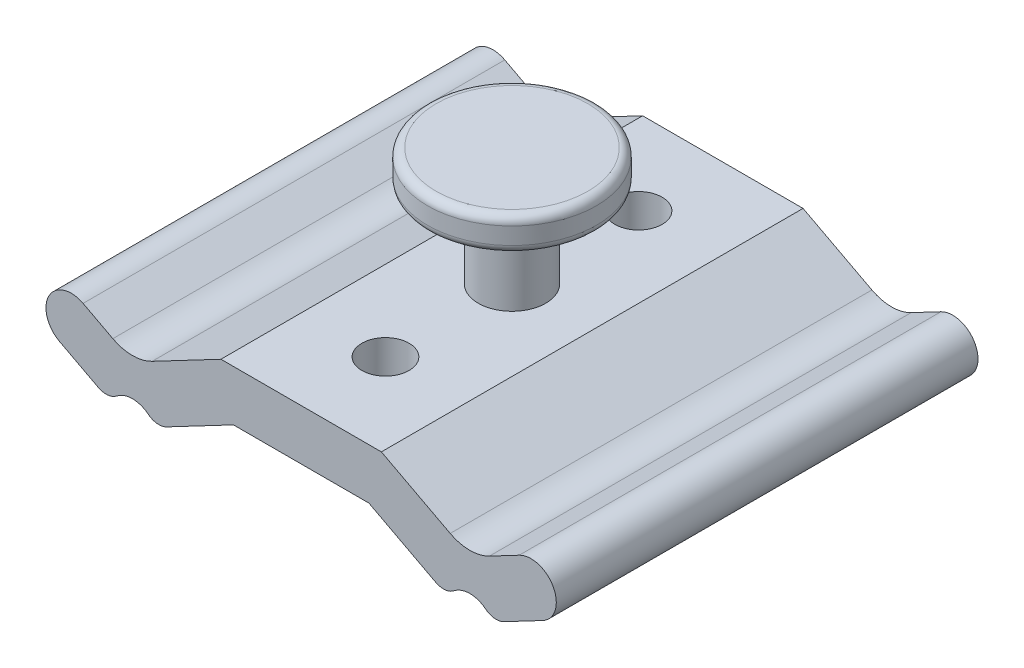
SolidWorks part; units mm, degrees
ref_plane "Front Plane" through (0, 0, 0) normal (0, 0, 1) x (1, 0, 0)
ref_plane "Top Plane" through (0, 0, 0) normal (0, 1, 0) x (1, 0, 0)
ref_plane "Right Plane" through (0, 0, 0) normal (1, 0, 0) x (0, 0, -1)
sketch "Croquis1" plane through (0, 0, 0) normal (0, 0, 1) x (1, 0, 0)
  line L0 (0, 0) -> (8.0292, 0)
  line L1 (8.0292, 0) -> (20, -6.3005)
  line L2 (20, -6.3005) -> (31.3055, -0.3502)
  line L3 (20, 5) -> (20, -6.3005) construction
  circle A1 centre (20, 5) radius 10 construction
  dimension "D1" = 5
  dimension "D3" = 20
  dimension "D2" = 124.482
  dimension "D4" = 20
extrude "Extruir-Lámina1" add sketch "Croquis1" against normal blind 25 and the other way blind 25 thin thin type one direction reverse wall 6
fillet "Redondeo1" radius 5 1 edges at (20, 0.4798, 0)
sketch "Croquis2" plane through (0, 0, 0) normal (0, 0, 1) x (1, 0, 0)
  circle A0 centre (20, -6.3005) radius 3
  dimension "D1" = 6
extrude "Cortar-Extruir1" cut sketch "Croquis2" against normal through all both and the other way through all
fillet "Redondeo2" 2 edges at (31.3055, -0.3502, 0) (28.5109, 4.9593, 0) type full round first side face at (26.9801, -2.6267, 0) second side face at (25.4199, 3.3324, 0) middle face at (29.9082, 2.3046, 0)
fillet "Redondeo3" radius 2 2 edges at (22.6547, -4.9033, 0) (17.3453, -4.9033, 0)
mirror "Simetría1" about plane through (0, 0, 0) normal (1, 0, 0) of "Redondeo3", "Redondeo2", "Redondeo1", "Cortar-Extruir1", "Extruir-Lámina1"
hole_wizard "Taladro2" positions "Croquis3" profile "Croquis4" legacy end condition through all
sketch "Croquis3" plane through (0, 6, 0) normal (0, 1, 0) x (1, 0, 0)
  line L0 (0, 15) -> (0, -15)
  point P1 (0, 15)
  point P2 (0, -15)
  dimension "D1" = 30
sketch "Croquis4" plane through (0, 6, -15) normal (1, 0, 0) x (0, 0, 1)
  line L0 (0, 0) -> (0, 10.3963)
  line L1 (0, 10.3963) -> (2.8, 10.3963)
  line L2 (2.8, 10.3963) -> (2.8, 0)
  line L3 (2.8, 0) -> (0, 0)
  line L4 (0, 110) -> (0, -10) construction
  dimension "Diámetro" = 5.6
  dimension "Profundidad" = 10.3963
sketch "Croquis5" plane through (0, 0, 0) normal (0, 0, 1) x (1, 0, 0)
  line L0 (0, 0) -> (0, 20)
  line L1 (0, 20) -> (10, 20)
  line L2 (10, 20) -> (10, 16)
  line L3 (10, 16) -> (4, 16)
  line L4 (4, 16) -> (4, 0)
  line L5 (-8.0292, 0) -> (8.0292, 0) construction
  line L6 (4, 0) -> (0, 0)
  dimension "D1" = 20
  dimension "D2" = 4
  dimension "D3" = 10
  dimension "D4" = 4
revolve "Revolución1" add sketch "Croquis5" angle 360 about L0
fillet "Redondeo4" radius 1 3 edges at (0, 16, -10) (0, 20, -10) (0, 16, -4)
